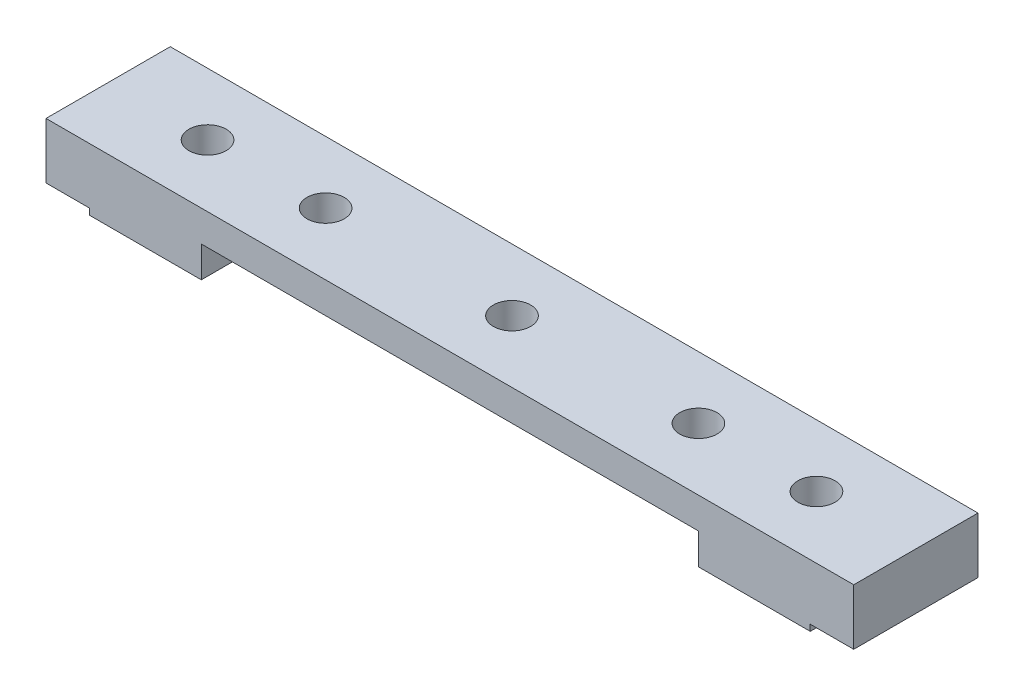
SolidWorks part; units mm, degrees
material "1060 Alloy"
ref_plane "Front Plane" through (0, 0, 0) normal (0, 0, 1) x (1, 0, 0)
ref_plane "Top Plane" through (0, 0, 0) normal (0, 1, 0) x (1, 0, 0)
ref_plane "Right Plane" through (0, 0, 0) normal (1, 0, 0) x (0, 0, -1)
sketch "Sketch1" plane through (0, 0, 0) normal (0, 1, 0) x (1, 0, 0)
  line L0 (32.5, 5) -> (32.5, 10) construction
  line L1 (0, 0) -> (65, 0)
  line L2 (0, 0) -> (0, 10)
  line L3 (0, 10) -> (65, 10)
  line L4 (65, 0) -> (65, 10)
  circle A0 centre (17.5, 5) radius 1.5
  circle A1 centre (32.5, 5) radius 1.5
  circle A2 centre (47.5, 5) radius 1.5
  dimension "D3" = 3
  dimension "D4" = 5
  dimension "D5" = 15
  dimension "D1" = 10
  dimension "D2" = 65
  dimension "D6" = 15
extrude "Boss-Extrude1" add sketch "Sketch1" along normal blind 5
sketch "Sketch2" plane through (0, 0, 0) normal (0, -1, 0) x (1, 0, 0)
  line L0 (0, 0) -> (65, 0) construction
  line L1 (12.5, 0) -> (52.5, 0)
  line L2 (12.5, 0) -> (12.5, -10)
  line L3 (12.5, -10) -> (52.5, -10)
  line L4 (52.5, 0) -> (52.5, -10)
  line L5 (65, -10) -> (0, -10) construction
  line L6 (0, -10) -> (0, 0) construction
  line L7 (65, 0) -> (65, -10) construction
  dimension "D1" = 12.5
  dimension "D2" = 12.5
extrude "Cut-Extrude1" cut sketch "Sketch2" against normal offset from surface (2.5 mm away) 2.5 up to face at (32.5, 5, -3.5)
sketch "Sketch3" plane through (0, 0, 0) normal (0, -1, 0) x (1, 0, 0)
  line L0 (12.5, -10) -> (0, -10) construction
  line L1 (0, 0) -> (3.5, 0)
  line L2 (0, 0) -> (0, -10)
  line L3 (0, -10) -> (3.5, -10)
  line L4 (3.5, 0) -> (3.5, -10)
  line L5 (65, -10) -> (52.5, -10) construction
  line L6 (65, 0) -> (61.5, 0)
  line L7 (65, 0) -> (65, -10)
  line L8 (65, -10) -> (61.5, -10)
  line L9 (61.5, 0) -> (61.5, -10)
  dimension "D1" = 3.5
  dimension "D2" = 3.5
extrude "Cut-Extrude2" cut sketch "Sketch3" against normal offset from surface (0.5 mm away) 4.5 up to face at (32.5, 5, -3.5)
sketch "Sketch4" plane through (0, 0, 0) normal (0, -1, 0) x (1, 0, 0)
  line L0 (3.5, -10) -> (3.5, 0) construction
  line L1 (3.5, 0) -> (12.5, 0) construction
  line L2 (61.5, 0) -> (61.5, -10) construction
  circle A0 centre (8, -5) radius 1.5
  circle A1 centre (57, -5) radius 1.5
  dimension "D1" = 3
  dimension "D2" = 4.5
  dimension "D3" = 5
  dimension "D4" = 4.5
extrude "Cut-Extrude3" cut sketch "Sketch4" against normal up to next
